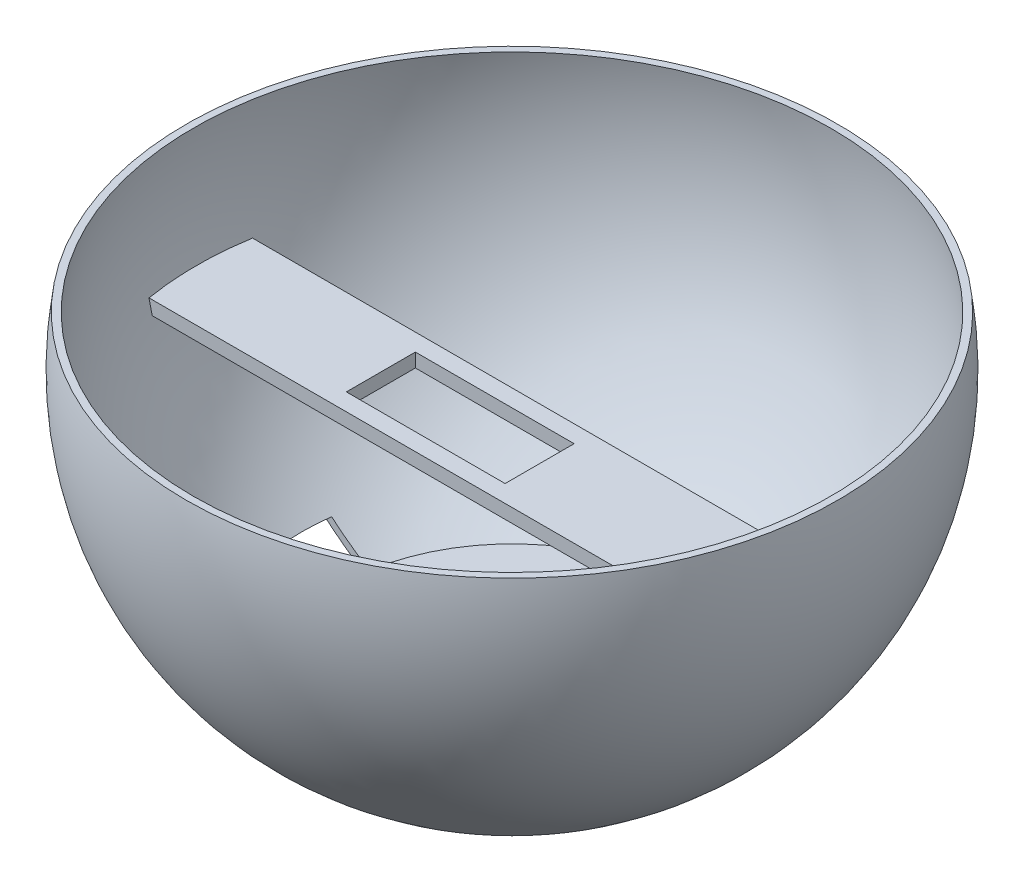
SolidWorks part; units mm, degrees
ref_plane "前视基准面" through (0, 0, 0) normal (0, 0, 1) x (1, 0, 0)
ref_plane "上视基准面" through (0, 0, 0) normal (0, 1, 0) x (1, 0, 0)
ref_plane "右视基准面" through (0, 0, 0) normal (1, 0, 0) x (0, 0, -1)
sketch "草图1" plane through (0, 0, 0) normal (1, 0, 0) x (0, 0, -1)
  line L0 (-47.2007, 7.2217) -> (0, 7.2217)
  line L1 (0, 7.2217) -> (0, -40.5137)
  line L2 (0, -40.5137) -> (-25.2725, -40.5137)
  arc A0 (-47.2007, 7.2217) -> (-25.2725, -40.5137) centre (0, 0) ccw
  dimension "D1" = 95.5
revolve "旋转1" add sketch "草图1" angle 360 about L1
shell "抽壳1" thickness 1 removed face at (0, 7.2217, 47.2007)
ref_plane "基准面1" through (0, -12.7783, 0) normal (0, 1, 0) x (1, 0, 0)
sketch "草图2" plane through (0, 0, 0) normal (1, 0, 0) x (0, 0, -1)
  line L0 (0, -9.7783) -> (0, 0) construction
  line L1 (-7.5, -9.7783) -> (7.5, -9.7783)
  line L2 (-7.5, -9.7783) -> (-7.5, -11.7783)
  line L3 (-7.5, -11.7783) -> (7.5, -11.7783)
  line L4 (7.5, -9.7783) -> (7.5, -11.7783)
  line L5 (-7.5, -9.7783) -> (0, 0) construction
  line L6 (0, 0) -> (7.5, -9.7783) construction
  line L7 (51.9208, -12.7783) -> (-51.9208, -12.7783) construction
  dimension "D1" = 15
  dimension "D2" = 2
  dimension "D3" = 1
extrude "凸台-拉伸1" add sketch "草图2" along normal up to next
sketch "草图4" plane through (0, 0, 0) normal (1, 0, 0) x (0, 0, -1)
  line L0 (0, -9.7783) -> (0, 0) construction
  line L1 (-7.5, -9.7783) -> (7.5, -9.7783)
  line L2 (-7.5, -9.7783) -> (-7.5, -11.7783)
  line L3 (-7.5, -11.7783) -> (7.5, -11.7783)
  line L4 (7.5, -9.7783) -> (7.5, -11.7783)
  line L5 (-7.5, -9.7783) -> (0, 0) construction
  line L6 (0, 0) -> (7.5, -9.7783) construction
  line L7 (51.9208, -12.7783) -> (-51.9208, -12.7783) construction
  dimension "D1" = 15
  dimension "D2" = 2
  dimension "D3" = 1
extrude "凸台-拉伸2" add sketch "草图4" against normal up to next
sketch "草图5" plane through (0, -9.7783, 0) normal (0, 1, 0) x (1, 0, 0)
  line L0 (0, 0) -> (0, -5) construction
  line L1 (4, -5) -> (-19, -5)
  line L2 (4, -5) -> (4, 5)
  line L3 (4, 5) -> (-19, 5)
  line L4 (-19, -5) -> (-19, 5)
  line L5 (0, -26.2545) -> (0, 26.2545) construction
  line L6 (0, 0) -> (0, 5) construction
  dimension "D1" = 10
  dimension "D2" = 4
  dimension "D3" = 23
extrude "切除-拉伸1" cut sketch "草图5" against normal blind 10
sketch "草图6" plane through (0, 0, 0) normal (1, 0, 0) x (0, 0, -1)
  line L0 (0, 0) -> (0, -35.5137) construction
  line L1 (4, -35.5137) -> (-4, -35.5137)
  line L2 (4, -35.5137) -> (4, -39.5137)
  line L3 (4, -39.5137) -> (-4, -39.5137)
  line L4 (-4, -35.5137) -> (-4, -39.5137)
  line L6 (-25.2725, -40.5137) -> (25.2725, -40.5137) construction
  dimension "D1" = 8
  dimension "D2" = 4
  dimension "D3" = 1
extrude "切除-拉伸2" cut sketch "草图6" against normal blind 47
